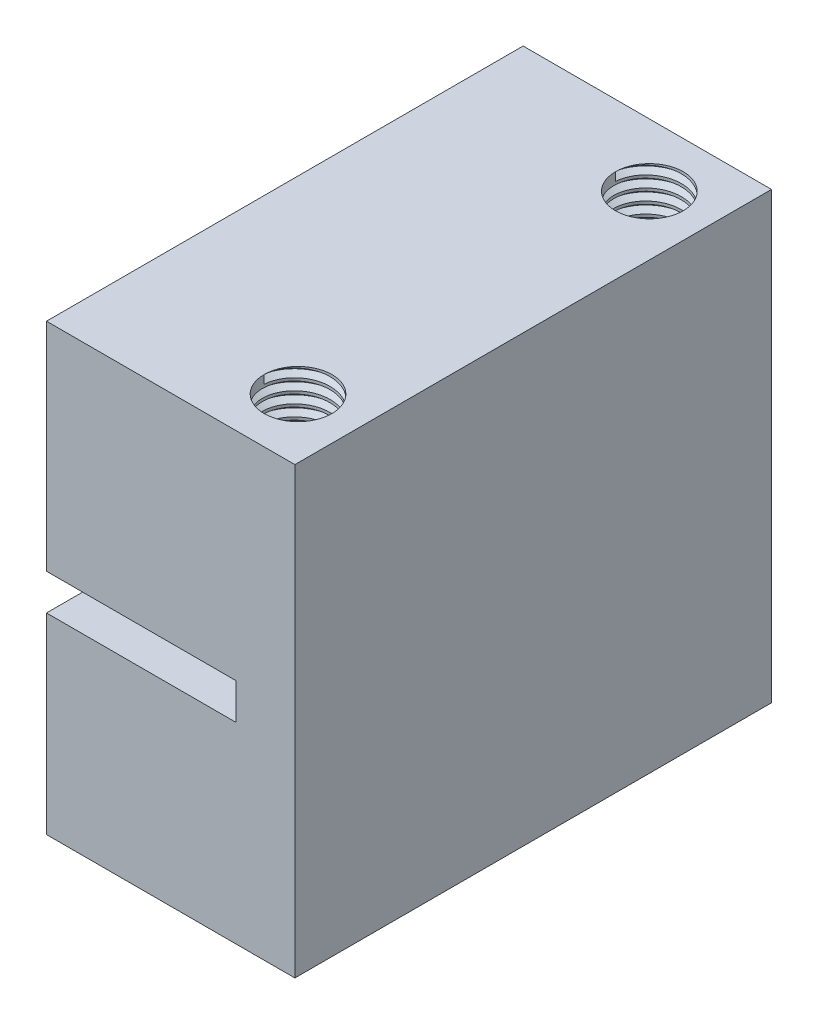
SolidWorks part; units mm, degrees
ref_plane "Front Plane" through (0, 0, 0) normal (0, 0, 1) x (1, 0, 0)
ref_plane "Top Plane" through (0, 0, 0) normal (0, 1, 0) x (1, 0, 0)
ref_plane "Right Plane" through (0, 0, 0) normal (1, 0, 0) x (0, 0, -1)
sketch "Sketch1" plane through (0, 0, 0) normal (0, 1, 0) x (1, 0, 0)
  line L1 (0, 0) -> (14, 0)
  line L2 (0, 0) -> (0, 20.0495)
  line L3 (0, 20.0495) -> (14, 20.0495)
  line L4 (14, 0) -> (14, 20.0495)
  dimension "D1" = 14
  dimension "D2" = 20.0495
extrude "Boss-Extrude1" add sketch "Sketch1" along normal blind 21.1074
sketch "Sketch2" plane through (0, 0, 0) normal (0, 0, 1) x (1, 0, 0)
  line L0 (0, 21.1074) -> (0, 0) construction
  line L1 (0, 10.1) -> (11.395, 10.1)
  line L2 (0, 10.1) -> (0, 8.5)
  line L3 (0, 8.5) -> (11.395, 8.5)
  line L4 (11.395, 10.1) -> (11.395, 8.5)
  line L5 (0, 0) -> (14, 0) construction
  line L7 (14, 21.1074) -> (14, 0) construction
  line L8 (0, 21.1074) -> (14, 21.1074)
  line L9 (0, 21.1074) -> (0, 19.69)
  line L10 (0, 19.69) -> (14, 19.69)
  line L11 (14, 21.1074) -> (14, 19.69)
  dimension "D1" = 1.6
  dimension "D2" = 8.5
  dimension "D3" = 2.605
  dimension "D4" = 9.59
extrude "Cut-Extrude1" cut sketch "Sketch2" against normal through all
sketch "Sketch3" plane through (0, 0, 0) normal (0, 0, 1) x (1, 0, 0)
  line L0 (0, 0) -> (14, 0) construction
  line L1 (0, 19.69) -> (3, 19.69)
  line L2 (0, 19.69) -> (0, 0)
  line L3 (0, 0) -> (3, 0)
  line L4 (3, 19.69) -> (3, 0)
  line L5 (14, 19.69) -> (14, 0) construction
  dimension "D1" = 11
extrude "Cut-Extrude2" cut sketch "Sketch3" against normal through all
sketch "Sketch4" plane through (0, 0, -20.0495) normal (0, 0, -1) x (-1, 0, 0)
  line L0 (-14, 0) -> (-3, 0) construction
  line L1 (-3, 0) -> (-3, 8.5) construction
  line L2 (-3, 8.5) -> (-11.395, 8.5) construction
  line L3 (-11.395, 8.5) -> (-11.395, 10.1) construction
  line L4 (-11.395, 10.1) -> (-3, 10.1) construction
  line L5 (-3, 10.1) -> (-3, 19.69) construction
  line L6 (-3, 19.69) -> (-14, 19.69) construction
  line L7 (-14, 19.69) -> (-14, 0) construction
  line L8 (-14, 0) -> (-3, 0)
  line L9 (-3, 0) -> (-3, 8.5)
  line L10 (-3, 8.5) -> (-11.395, 8.5)
  line L11 (-11.395, 8.5) -> (-11.395, 10.1)
  line L12 (-11.395, 10.1) -> (-3, 10.1)
  line L13 (-3, 10.1) -> (-3, 19.69)
  line L14 (-3, 19.69) -> (-14, 19.69)
  line L15 (-14, 19.69) -> (-14, 0)
extrude "Boss-Extrude2" add sketch "Sketch4" along normal blind 1.0579
sketch "Sketch5" plane through (0, 19.69, 0) normal (0, 1, 0) x (1, 0, 0)
  line L0 (3, 21.1074) -> (14, 21.1074) construction
  line L2 (14, 21.1074) -> (14, 0) construction
  line L3 (14, 21.1074) -> (11.3647, 18.3325) construction
  line L4 (14, 0) -> (11.3647, 2.775) construction
  circle A0 centre (11.3647, 18.3325) radius 1.5
  circle A1 centre (11.3647, 2.775) radius 1.5
  dimension "D3" = 3
  dimension "D1" = 2.775
  dimension "D2" = 2.6353
extrude "Cut-Extrude3" cut sketch "Sketch5" against normal blind 8
thread "Thread1" pitch 0.5 method cut profile "Thread Profile1" start angle 0, offset 0, length 8, pitch 0.5, diameter 3
ref_plane "Plane2" through (9.8647, 19.69, -2.775) normal (0, 0, 1) x (-1, 0, 0)
sketch "Thread Profile1" plane through (9.8647, 19.69, -2.775) normal (0, 0, 1) x (-1, 0, 0)
  line L0 (0, 0) -> (0, 0.5) construction
  line L1 (0, 0) -> (0.2706, 0.1562)
  line L2 (0.2706, 0.1562) -> (0.2706, 0.2187)
  line L3 (0.2706, 0.2187) -> (0, 0.375)
  line L4 (0.2706, 0.1875) -> (0, 0.1875) construction
  line L11 (0, 0) -> (0, 0.375)
  point P2 (0, 0)
  dimension "Pitch" = 0.5
  dimension "Profile_Angle" = 60
  dimension "Profile_Land" = 0.0625
  dimension "Profile_Height" = 0.2706
thread "Thread2" pitch 0.5 method cut profile "Thread Profile2" start angle 0, offset 0, length 8, pitch 0.5, diameter 3
ref_plane "Plane3" through (9.8647, 19.69, -18.3325) normal (0, 0, 1) x (-1, 0, 0)
sketch "Thread Profile2" plane through (9.8647, 19.69, -18.3325) normal (0, 0, 1) x (-1, 0, 0)
  line L0 (0, 0) -> (0, 0.5) construction
  line L1 (0, 0) -> (0.2706, 0.1562)
  line L2 (0.2706, 0.1562) -> (0.2706, 0.2187)
  line L3 (0.2706, 0.2187) -> (0, 0.375)
  line L4 (0.2706, 0.1875) -> (0, 0.1875) construction
  line L11 (0, 0) -> (0, 0.375)
  point P2 (0, 0)
  dimension "Pitch" = 0.5
  dimension "Profile_Angle" = 60
  dimension "Profile_Land" = 0.0625
  dimension "Profile_Height" = 0.2706
sketch "Sketch13" plane through (0, 0, 0) normal (0, -1, 0) x (-1, 0, 0)
  line L1 (-14, 21.1074) -> (-3, 21.1074) construction
  line L2 (-14, 21.1074) -> (-14, 0) construction
  line L3 (-14, 0) -> (-3, 0) construction
  line L4 (-3, 21.1074) -> (-3, 0) construction
  line L5 (-14, 21.1074) -> (-3, 0) construction
  line L6 (-14, 0) -> (-3, 21.1074) construction
  line L7 (-9.1932, 11.8839) -> (-8.5, 12.2832)
  line L8 (-8.5, 12.2832) -> (-7.8068, 11.8839)
  arc A0 (-9.1932, 11.8839) -> (-7.8068, 11.8839) centre (-8.5, 10.5537) ccw
  point P0 (-8.5, 10.5537)
  point P8 (0, 0)
  point P13 (-8.5, 12.6262)
  point P14 (-7.8068, 11.8839)
  point P15 (-8.5, 12.2384)
  dimension "D1" = 3
  dimension "D2" = 0.8
extrude "Cut-Extrude4" cut sketch "Sketch13" against normal blind 7
